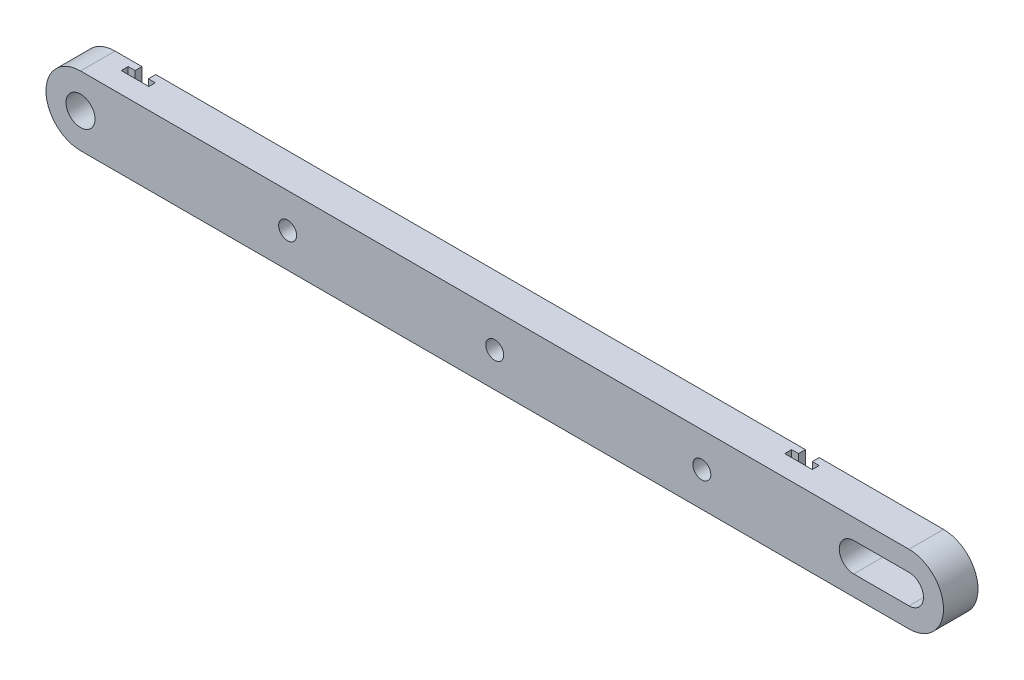
SolidWorks part; units mm, degrees
ref_plane "Plan de face" through (0, 0, 0) normal (0, 0, 1) x (1, 0, 0)
ref_plane "Plan de dessus" through (0, 0, 0) normal (0, 1, 0) x (1, 0, 0)
ref_plane "Plan de droite" through (0, 0, 0) normal (1, 0, 0) x (0, 0, -1)
sketch "Esquisse1" plane through (0, 0, 0) normal (0, 0, 1) x (1, 0, 0)
  line L0 (600, 0) -> (0, 0) construction
  line L1 (600, -25) -> (0, -25)
  line L2 (600, 25) -> (0, 25)
  line L3 (560, 0) -> (600, 0) construction
  line L4 (560, 10.5) -> (600, 10.5)
  line L5 (560, -10.5) -> (600, -10.5)
  line L6 (300, 50.6124) -> (300, -48.183) construction
  line L7 (290, -25) -> (290, -20)
  line L8 (290, -20) -> (282.5, -20)
  line L9 (282.5, -20) -> (282.5, -15)
  line L10 (282.5, -15) -> (317.5, -15)
  line L11 (317.5, -15) -> (317.5, -20)
  line L12 (317.5, -20) -> (310, -20)
  line L13 (310, -20) -> (310, -25)
  line L14 (537.5, -15) -> (555, -15)
  line L15 (555, -15) -> (555, -25)
  line L16 (45, -15) -> (45, -25)
  line L18 (545, -25) -> (545, -20)
  line L19 (545, -20) -> (537.5, -20)
  line L20 (537.5, -20) -> (537.5, -15)
  line L21 (45, -15) -> (62.5, -15)
  line L22 (62.5, -15) -> (62.5, -20)
  line L23 (62.5, -20) -> (55, -20)
  line L24 (55, -20) -> (55, -25)
  line L30 (27.5, -20) -> (27.5, -15) [skipped]
  line L31 (35, -20) -> (27.5, -20) [skipped]
  line L32 (572.5, -15) -> (572.5, -20) [skipped]
  line L33 (572.5, -20) -> (565, -20) [skipped]
  line L34 (565, -20) -> (565, -25) [skipped]
  line L35 (35, -25) -> (35, -20) [skipped]
  arc A0 (600, -25) -> (600, 25) centre (600, 0) ccw
  arc A1 (0, 25) -> (0, -25) centre (0, 0) ccw
  circle A3 centre (0, 0) radius 10.5
  arc A4 (560, 10.5) -> (560, -10.5) centre (560, 0) ccw
  arc A5 (600, -10.5) -> (600, 10.5) centre (600, 0) ccw
  circle A6 centre (300, 0) radius 10
  circle A7 centre (300, 0) radius 6.5
  circle A8 centre (450, 0) radius 10
  circle A9 centre (450, 0) radius 6.5
  circle A10 centre (150, 0) radius 10
  circle A11 centre (150, 0) radius 6.5
  point P2 (300, 0)
  point P11 (580, 0)
  dimension "D2" = 25
  dimension "D3" = 40
  dimension "D4" = 0
  dimension "D1" = 10.5
  dimension "D8" = 21
  dimension "D9" = 10
  dimension "D6" = 560
  dimension "D19" = 13
  dimension "D20" = 20
  dimension "D23" = 150
  dimension "D24" = 150
  dimension "D5" = 0
  dimension "D7" = 0
  dimension "D10" = 20
  dimension "D11" = 35
  dimension "D12" = 5
  dimension "D13" = 10
  dimension "D16" = 220
  dimension "D17" = 220
  dimension "D18" = 17.5
  dimension "D25" = 17.5
  dimension "D26" = 10
  dimension "D14" = 2
  dimension "D15" = 2
  dimension "D21" = 2
  dimension "D22" = 2
extrude "Boss.-Extru.1" add sketch "Esquisse1" along normal blind 25 contours L2 A1 L1 A0 | A3 | L5 A5 L4 A4
sketch "Esquisse2" plane through (0, 25, 0) normal (0, 1, 0) x (1, 0, 0)
  line L6 (510, 0) -> (500, 0)
  line L11 (500, 0) -> (500, -5)
  line L16 (600, 0) -> (0, 0) construction
  line L21 (500, -5) -> (495, -5)
  line L22 (495, -5) -> (495, -10)
  line L23 (495, -10) -> (515, -10)
  line L26 (515, -5) -> (515, -10)
  line L27 (510, -5) -> (515, -5)
  line L28 (510, 0) -> (510, -5)
  line L29 (600, -25) -> (600, 0) construction
  dimension "D1" = 10
  dimension "D2" = 85
  dimension "D3" = 20
  dimension "D4" = 5
  dimension "D6" = 5
  dimension "D7" = 10
extrude "Enlèv. mat.-Extru.1" cut sketch "Esquisse2" against normal blind 35 contours L28 L27 L26 L23 L22 L21 L11 L6
sketch "Esquisse3" plane through (0, 25, 0) normal (0, 1, 0) x (1, 0, 0)
  line L0 (19.4971, 0) -> (19.4971, -5)
  line L1 (500, 0) -> (0, 0) construction
  line L2 (19.4971, -5) -> (14.4971, -5)
  line L3 (14.4971, -5) -> (14.4971, -10)
  line L4 (14.4971, -10) -> (34.4971, -10)
  line L5 (34.4971, -10) -> (34.4971, -5.3579)
  line L6 (34.4971, -5.3579) -> (29.4971, -5.3579)
  line L7 (29.4971, -5.3579) -> (29.4971, 0)
  line L8 (29.4971, 0) -> (19.4971, 0)
  line L9 (0, -25) -> (0, 0) construction
  dimension "D1" = 20
  dimension "D2" = 10
  dimension "D3" = 5
  dimension "D4" = 10
  dimension "D5" = 19.4971
extrude "Enlèv. mat.-Extru.2" cut sketch "Esquisse3" against normal blind 50
extrude "Enlèv. mat.-Extru.3" cut sketch "Esquisse1<3>" along normal blind 15 contours L13 L12 L11 L10 L9 L8 L7 L1 | L1 L24 L23 L22 L21 | L20 L19 L18 L1 L14 region at (547.6136, -19.3182, 0) region at (300, -19.3182, 0) region at (52.3864, -19.3182, 0)
sketch "Esquisse1<3>" plane through (0, 0, 0) normal (0, 0, 1) x (1, 0, 0) same geometry as "Esquisse1"
extrude "Enlèv. mat.-Extru.4" cut sketch "Esquisse1<4>" along normal through all contours A11 | A7 | A9
sketch "Esquisse1<4>" plane through (0, 0, 0) normal (0, 0, 1) x (1, 0, 0) same geometry as "Esquisse1"
extrude "Enlèv. mat.-Extru.5" cut sketch "Esquisse1<5>" along normal blind 12 contours A6 | A8 | A10
sketch "Esquisse1<5>" plane through (0, 0, 0) normal (0, 0, 1) x (1, 0, 0) same geometry as "Esquisse1"
